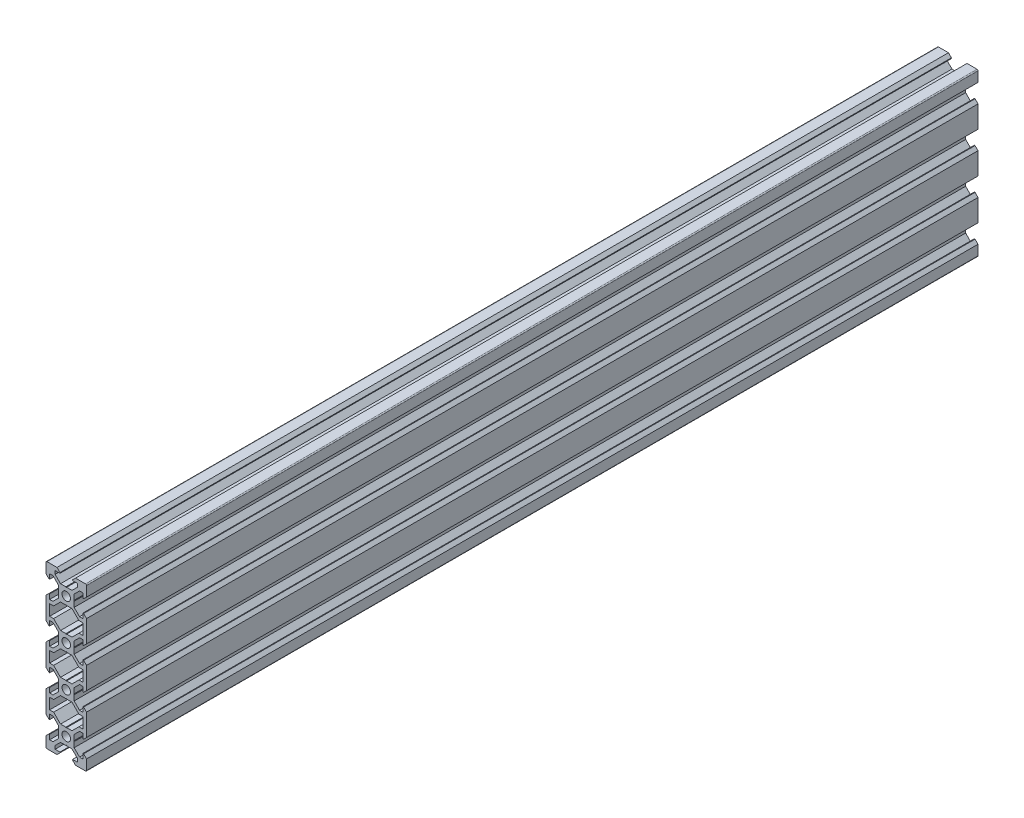
SolidWorks part; units mm, degrees
ref_plane "Plan de face" through (0, 0, 0) normal (0, 0, 1) x (1, 0, 0)
ref_plane "Plan de dessus" through (0, 0, 0) normal (0, 1, 0) x (1, 0, 0)
ref_plane "Plan de droite" through (0, 0, 0) normal (1, 0, 0) x (0, 0, -1)
ref_axis "Axe" through (0, 0, -13.782) along (0, 0, 1)
sketch "Esquisse1" plane through (0, 0, 0) normal (0, 0, 1) x (1, 0, 0)
  line L0 (0, 27.6392) -> (0, -27.6392) construction
  line L1 (-33.6074, 0) -> (33.6074, 0) construction
  line L2 (0, 0) -> (-22.2114, 22.2114) construction
  line L3 (-9.5, 10) -> (-4.58, 10)
  line L4 (-4.58, 10) -> (-3.125, 8.545)
  line L5 (-3.125, 8.545) -> (-3.125, 8.2)
  line L6 (-3.125, 8.2) -> (-5.5, 8.2)
  line L7 (-2.8393, 3.9) -> (-5.5, 6.5607)
  line L8 (-2.8393, 3.9) -> (-0.21, 3.9)
  line L9 (-5.5, 6.5607) -> (-5.5, 8.2)
  line L10 (0, 3.69) -> (0, 2.1)
  line L11 (-3.9, 2.8393) -> (-6.5607, 5.5)
  line L12 (-8.545, 3.125) -> (-8.2, 3.125)
  line L13 (-8.2, 3.125) -> (-8.2, 5.5)
  line L14 (-6.5607, 5.5) -> (-8.2, 5.5)
  line L15 (-10, 4.58) -> (-8.545, 3.125)
  line L16 (-10, 9.5) -> (-10, 4.58)
  line L17 (-0.21, 3.9) -> (0, 3.69)
  line L18 (-3.9, 2.8393) -> (-3.9, 0.21)
  line L19 (-6.2393, -12.7) -> (-8.2, -12.7)
  line L20 (-3.9, 0.21) -> (-3.69, 0)
  line L21 (-0.21, -3.9) -> (0, -3.69)
  line L22 (0, -3.69) -> (0, -2.1)
  line L23 (-6.5607, -5.5) -> (-8.2, -5.5)
  line L24 (-2.8393, -3.9) -> (-0.21, -3.9)
  line L25 (-8.545, -3.125) -> (-8.2, -3.125)
  line L26 (-10, -4.58) -> (-8.545, -3.125)
  line L27 (-8.2, -3.125) -> (-8.2, -5.5)
  line L28 (-2.8393, -3.9) -> (-6.2393, -7.3)
  line L29 (-3.9, -2.8393) -> (-6.5607, -5.5)
  line L30 (-3.9, -2.8393) -> (-3.9, -0.21)
  line L31 (-3.9, -0.21) -> (-3.69, 0)
  line L32 (-6.2393, -7.3) -> (-8.2, -7.3)
  line L33 (-8.2, -7.3) -> (-8.2, -12.7)
  line L34 (-8.2, -10) -> (-10, -10) construction
  line L35 (-10, -15.42) -> (-10, -4.58)
  line L36 (-3.9, -19.79) -> (-3.69, -20)
  line L37 (-3.9, -17.1607) -> (-3.9, -19.79)
  line L38 (-3.9, -17.1607) -> (-6.5607, -14.5)
  line L39 (-2.8393, -16.1) -> (-6.2393, -12.7)
  line L40 (-8.2, -16.875) -> (-8.2, -14.5)
  line L41 (-10, -15.42) -> (-8.545, -16.875)
  line L42 (-8.545, -16.875) -> (-8.2, -16.875)
  line L43 (-2.8393, -16.1) -> (-0.21, -16.1)
  line L44 (-6.5607, -14.5) -> (-8.2, -14.5)
  line L45 (0, -16.31) -> (0, -17.9)
  line L46 (-0.21, -16.1) -> (0, -16.31)
  line L47 (-8.2, -30) -> (-10, -30) construction
  line L48 (-3.69, -20) -> (0, -20) construction
  line L49 (-0.21, -23.9) -> (0, -23.69)
  line L50 (0, -23.69) -> (0, -22.1)
  line L51 (-6.5607, -25.5) -> (-8.2, -25.5)
  line L52 (-2.8393, -23.9) -> (-0.21, -23.9)
  line L53 (-8.545, -23.125) -> (-8.2, -23.125)
  line L54 (-10, -24.58) -> (-8.545, -23.125)
  line L55 (-8.2, -23.125) -> (-8.2, -25.5)
  line L56 (-2.8393, -23.9) -> (-6.2393, -27.3)
  line L57 (-3.9, -22.8393) -> (-6.5607, -25.5)
  line L58 (-3.9, -22.8393) -> (-3.9, -20.21)
  line L59 (-3.9, -20.21) -> (-3.69, -20)
  line L60 (-10, -24.58) -> (-10, -35.42)
  line L61 (-8.2, -32.7) -> (-8.2, -27.3)
  line L62 (-3.69, -40) -> (0, -40) construction
  line L63 (-8.2, -50) -> (-10, -50) construction
  line L64 (0, -60) -> (-22.2114, -82.2114) construction
  line L65 (-33.6074, -60) -> (33.6074, -60) construction
  line L66 (0, -87.6392) -> (0, -32.3608) construction
  line L67 (-6.2393, -32.7) -> (-8.2, -32.7)
  line L68 (-3.9, -39.79) -> (-3.69, -40)
  line L69 (-3.9, -37.1607) -> (-3.9, -39.79)
  line L70 (-3.9, -37.1607) -> (-6.5607, -34.5)
  line L71 (-2.8393, -36.1) -> (-6.2393, -32.7)
  line L72 (-8.2, -36.875) -> (-8.2, -34.5)
  line L73 (-10, -35.42) -> (-8.545, -36.875)
  line L74 (-8.545, -36.875) -> (-8.2, -36.875)
  line L75 (-6.2393, -27.3) -> (-8.2, -27.3)
  line L76 (-2.8393, -36.1) -> (-0.21, -36.1)
  line L77 (-6.5607, -34.5) -> (-8.2, -34.5)
  line L78 (0, -36.31) -> (0, -37.9)
  line L79 (-0.21, -36.1) -> (0, -36.31)
  line L80 (-0.21, -43.9) -> (0, -43.69)
  line L81 (0, -43.69) -> (0, -42.1)
  line L82 (-6.5607, -45.5) -> (-8.2, -45.5)
  line L83 (-2.8393, -43.9) -> (-0.21, -43.9)
  line L84 (-8.545, -43.125) -> (-8.2, -43.125)
  line L85 (-10, -44.58) -> (-8.545, -43.125)
  line L86 (-8.2, -43.125) -> (-8.2, -45.5)
  line L87 (-2.8393, -43.9) -> (-6.2393, -47.3)
  line L88 (-3.9, -42.8393) -> (-6.5607, -45.5)
  line L89 (-3.9, -42.8393) -> (-3.9, -40.21)
  line L90 (-3.9, -40.21) -> (-3.69, -40)
  line L91 (-10, -44.58) -> (-10, -55.42)
  line L92 (-8.2, -52.7) -> (-8.2, -47.3)
  line L93 (-6.2393, -52.7) -> (-8.2, -52.7)
  line L94 (-3.9, -59.79) -> (-3.69, -60)
  line L95 (-3.9, -57.1607) -> (-3.9, -59.79)
  line L96 (-3.9, -57.1607) -> (-6.5607, -54.5)
  line L97 (-2.8393, -56.1) -> (-6.2393, -52.7)
  line L98 (-8.2, -56.875) -> (-8.2, -54.5)
  line L99 (-10, -55.42) -> (-8.545, -56.875)
  line L100 (-8.545, -56.875) -> (-8.2, -56.875)
  line L101 (-2.8393, -56.1) -> (-0.21, -56.1)
  line L102 (-6.5607, -54.5) -> (-8.2, -54.5)
  line L103 (0, -56.31) -> (0, -57.9)
  line L104 (-0.21, -56.1) -> (0, -56.31)
  line L105 (-3.9, -60.21) -> (-3.69, -60)
  line L106 (-6.2393, -47.3) -> (-8.2, -47.3)
  line L107 (-3.9, -62.8393) -> (-3.9, -60.21)
  line L108 (-0.21, -63.9) -> (0, -63.69)
  line L109 (-10, -69.5) -> (-10, -64.58)
  line L110 (-10, -64.58) -> (-8.545, -63.125)
  line L111 (-6.5607, -65.5) -> (-8.2, -65.5)
  line L112 (-8.2, -63.125) -> (-8.2, -65.5)
  line L113 (-8.545, -63.125) -> (-8.2, -63.125)
  line L114 (-3.9, -62.8393) -> (-6.5607, -65.5)
  line L115 (0, -63.69) -> (0, -62.1)
  line L116 (-5.5, -66.5607) -> (-5.5, -68.2)
  line L117 (-2.8393, -63.9) -> (-0.21, -63.9)
  line L118 (-2.8393, -63.9) -> (-5.5, -66.5607)
  line L119 (-3.125, -68.2) -> (-5.5, -68.2)
  line L120 (-3.125, -68.545) -> (-3.125, -68.2)
  line L121 (-4.58, -70) -> (-3.125, -68.545)
  line L122 (-9.5, -70) -> (-4.58, -70)
  arc A0 (0, -2.1) -> (0, 2.1) centre (0, 0) cw
  arc A1 (-9.5, 10) -> (-10, 9.5) centre (-9.5, 9.5) ccw
  arc A2 (0, -42.1) -> (0, -37.9) centre (0, -40) cw
  arc A3 (-9.5, -70) -> (-10, -69.5) centre (-9.5, -69.5) cw
  arc A4 (0, -17.9) -> (0, -22.1) centre (0, -20) ccw
  arc A5 (0, -57.9) -> (0, -62.1) centre (0, -60) ccw
  point P4 (0, 0)
  point P7 (0, 0)
  point P30 (-10, 10)
  point P60 (0, -20)
  point P146 (-10, -70)
  dimension "D5" = 11
  dimension "D2" = 2.1
  dimension "D3" = 6.25
  dimension "D10" = 0.5
  dimension "D4" = 9.16
  dimension "D6" = 1.5
  dimension "D7" = 1.8
  dimension "D8" = 4.3
  dimension "D9" = 20
  dimension "D11" = 0.42
  dimension "D12" = 10
  dimension "D13" = 1.8
extrude "Boss.-Extru.1" add sketch "Esquisse1" along normal blind 440
sketch "Esquisse3" plane through (0, 0, 440) normal (0, 0, 1) x (1, 0, 0)
  line L0 (0, 0) -> (-9.8536, 9.8536) construction
  line L1 (-8.2, 8.2) -> (-8.2, 6.57)
  line L2 (-8.2, 6.57) -> (-7.54, 6.57)
  line L3 (-7.54, 6.57) -> (-6.57, 7.54)
  line L4 (-8.2, 3.125) -> (-8.2, 5.5) construction
  line L5 (-6.57, 8.2) -> (-6.57, 7.54)
  line L6 (-8.2, 8.2) -> (-6.57, 8.2)
  line L7 (-5.5, 6.5607) -> (-5.5, 8.2) construction
  line L8 (-10, -30) -> (6.918, -30) construction
  line L9 (-10, -24.58) -> (-10, -35.42) construction
  line L10 (-8.2, -68.2) -> (-6.57, -68.2)
  line L11 (-6.57, -68.2) -> (-6.57, -67.54)
  line L12 (-7.54, -66.57) -> (-6.57, -67.54)
  line L13 (-8.2, -66.57) -> (-7.54, -66.57)
  line L14 (-8.2, -68.2) -> (-8.2, -66.57)
  arc A0 (-9.5, 10) -> (-10, 9.5) centre (-9.5, 9.5) ccw construction
  point P13 (-7.055, 7.055)
  point P14 (-6.57, 7.87)
  point P26 (-7.055, -67.055)
  dimension "D1" = 1.07
extrude "Enlèv. mat.-Extru.1" [suppressed] cut sketch "Esquisse3" against normal through all
mirror "Symétrie1" of "Enlèv. mat.-Extru.1", "Boss.-Extru.1"
